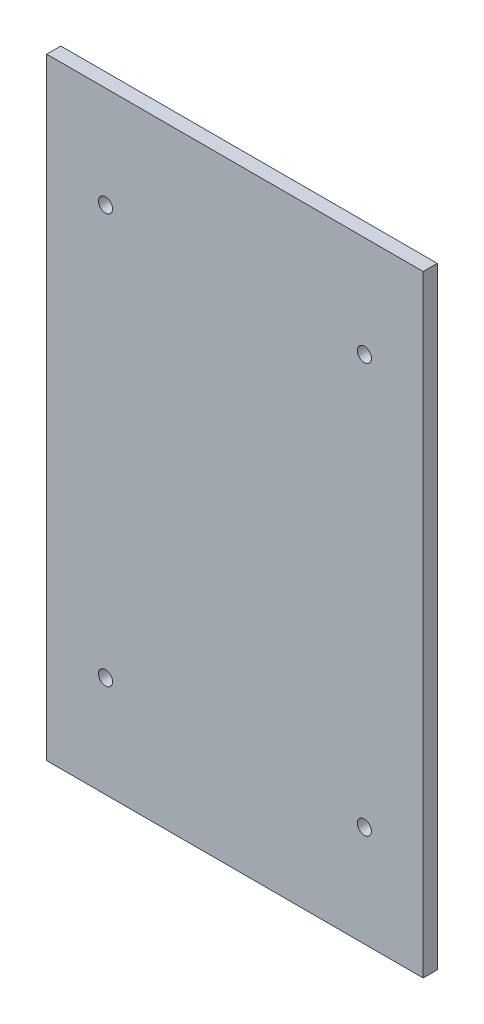
SolidWorks part; units mm, degrees
ref_plane "Plano frontal" through (0, 0, 0) normal (0, 0, 1) x (1, 0, 0)
ref_plane "Plano superior" through (0, 0, 0) normal (0, 1, 0) x (1, 0, 0)
ref_plane "Plano direito" through (0, 0, 0) normal (1, 0, 0) x (0, 0, -1)
sketch "Esboço1" plane through (0, 0, 0) normal (0, 0, 1) x (1, 0, 0)
  line L1 (-67.5, 35.688) -> (12.5, 35.688)
  line L2 (-67.5, 35.688) -> (-67.5, -94.312)
  line L3 (-67.5, -94.312) -> (12.5, -94.312)
  line L4 (12.5, 35.688) -> (12.5, -94.312)
  line L6 (-55, 35.688) -> (-55, -94.312)
  line L7 (0, 35.688) -> (0, -94.312)
  line L10 (-67.5, 14.188) -> (12.5, 14.188)
  line L11 (-67.5, -72.812) -> (12.5, -72.812)
  point P4 (0, 30.9244)
  point P13 (-67.5426, 30.7992)
  point P14 (0, 0)
  point P15 (0, -94.312)
  dimension "D1" = 80
  dimension "D2" = 130
  dimension "D3" = 12.5
  dimension "D4" = 12.5
  dimension "D5" = 21.5
  dimension "D6" = 21.5
extrude "Ressalto-extrusão1" add sketch "Esboço1" along normal blind 3 contours L2 L3 L4 L1
sketch "Esboço2" plane through (0, 0, 3) normal (0, 0, 1) x (1, 0, 0)
  line L0 (-55, 35.688) -> (-67.5, 35.688)
  line L1 (-67.5, 35.688) -> (12.5, 35.688) construction
  line L2 (-67.5, 35.688) -> (-67.5, 14.188)
  line L3 (-67.5, 35.688) -> (-67.5, -94.312) construction
  line L4 (-67.5, 14.188) -> (12.5, 14.188)
  line L5 (12.5, 35.688) -> (12.5, -94.312) construction
  line L6 (-55, 35.688) -> (-55, -94.312)
  line L7 (-67.5, -94.312) -> (12.5, -94.312) construction
  line L8 (12.5, 35.688) -> (0, 35.688)
  line L9 (12.5, 35.688) -> (12.5, 14.188)
  line L10 (0, 35.688) -> (0, -94.312)
  line L11 (12.5, -72.812) -> (12.5, -94.312)
  line L12 (12.5, -72.812) -> (-67.5, -72.812)
  circle A0 centre (-55, 14.188) radius 1.5
  circle A1 centre (0, 14.188) radius 1.5
  circle A2 centre (0, -72.812) radius 1.5
  circle A3 centre (-55, -72.812) radius 1.5
  dimension "D5" = 3
  dimension "D6" = 3
  dimension "D7" = 3
  dimension "D8" = 3
  dimension "D1" = 12.5
  dimension "D2" = 21.5
  dimension "D3" = 12.5
  dimension "D4" = 21.5
extrude "Corte-extrusão1" cut sketch "Esboço2" against normal blind 3 contours A0
extrude "Corte-extrusão2" cut sketch "Esboço2<3>" against normal blind 3 contours A1
sketch "Esboço2<3>" plane through (0, 0, 3) normal (0, 0, 1) x (1, 0, 0) same geometry as "Esboço2"
extrude "Corte-extrusão3" cut sketch "Esboço2<4>" against normal blind 3 contours A3 | A2
sketch "Esboço2<4>" plane through (0, 0, 3) normal (0, 0, 1) x (1, 0, 0) same geometry as "Esboço2"
